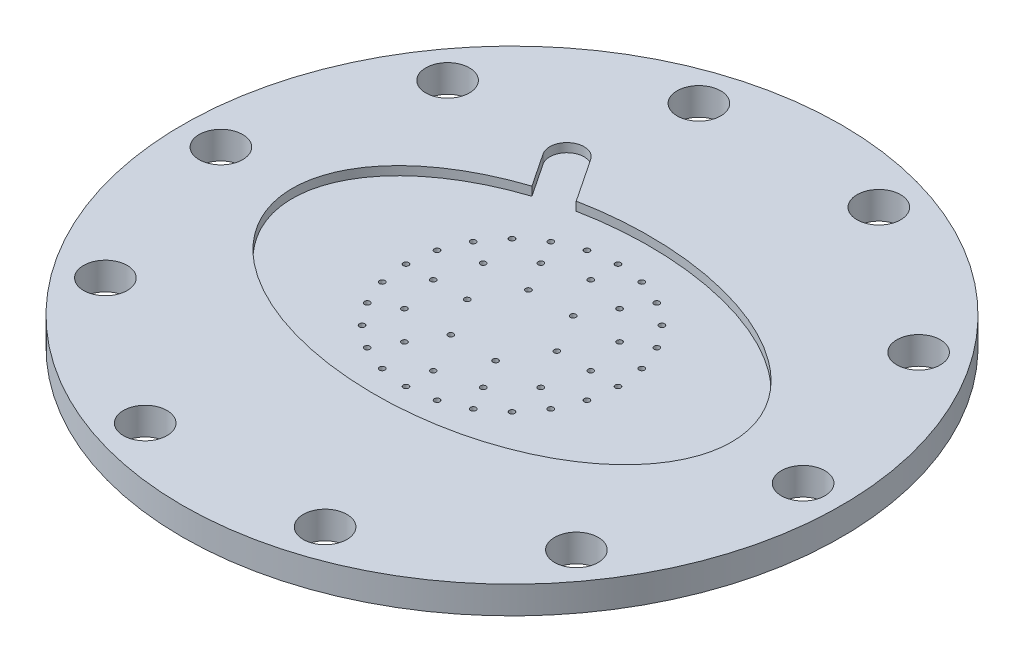
SolidWorks part; units mm, degrees
ref_plane "Front Plane" through (0, 0, 0) normal (0, 0, 1) x (1, 0, 0)
ref_plane "Top Plane" through (0, 0, 0) normal (0, 1, 0) x (1, 0, 0)
ref_plane "Right Plane" through (0, 0, 0) normal (1, 0, 0) x (0, 0, -1)
sketch "Sketch1" plane through (0, 0, 0) normal (0, 0, 1) x (1, 0, 0)
  line L0 (0, -6.35) -> (54.8259, -6.35)
  line L1 (0, 0) -> (76.2, 0)
  line L2 (0, 0) -> (0, -6.35)
  line L4 (76.2, 0) -> (76.2, -6.35)
  line L5 (54.8259, -6.35) -> (54.8259, -3.6576)
  line L6 (54.8259, -3.6576) -> (58.8899, -3.6576)
  line L7 (58.8899, -3.6576) -> (58.8899, -6.35)
  line L8 (58.8899, -6.35) -> (76.2, -6.35)
  dimension "D1" = 6.35
  dimension "D2" = 76.2
  dimension "D3" = 58.8899
  dimension "D4" = 4.064
  dimension "D5" = 2.6924
revolve "Revolve1" add sketch "Sketch1" angle 360 about L2
sketch "Sketch2" plane through (0, 0, 0) normal (0, 1, 0) x (1, 0, 0)
  line L0 (0, 0) -> (67.31, 0) construction
  dimension "D1" = 67.31
ref_axis "Axis1" through (0, 0.3175, 0) along (0, -1, 0)
hole_wizard "3/8 Clearance Hole1" positions "3DSketch2" profile "Sketch4" hole size "3/8" standard "ANSI Inch" end condition through all
sketch3d "3DSketch2"
  point P0 (67.31, 0, 0)
sketch "Sketch4" plane through (67.31, 0, 0) normal (1, 0, 0) x (0, 0, 1)
  line L0 (0, 0) -> (0, 6.35)
  line L1 (0, 6.35) -> (5.0419, 6.35)
  line L2 (5.0419, 6.35) -> (5.0419, 0)
  line L5 (5.0419, 0) -> (0, 0)
  line L11 (0, -6.35) -> (0, 107.95) construction
  dimension "Thru Hole Dia." = 10.0838
  dimension "Thru Hole Depth" = 6.35
pattern_circular "CirPattern1" count 10 over 360 about axis through (0, 0.3175, 0) along (0, -1, 0) of "3/8 Clearance Hole1"
sketch "Sketch5" plane through (0, 0, 0) normal (0, 1, 0) x (1, 0, 0)
  line L0 (-50.8, 0) -> (50.8, 0) construction
  line L1 (0, 0) -> (-25.4, 38.1) construction
  line L2 (-3.3022, -2.2015) -> (-28.7022, 35.8985)
  line L3 (3.3022, 2.2015) -> (-22.0978, 40.3015)
  arc A0 (-3.3022, -2.2015) -> (3.3022, 2.2015) centre (0, 0) ccw
  arc A1 (-22.0978, 40.3015) -> (-28.7022, 35.8985) centre (-25.4, 38.1) ccw
  ellipse E0 centre (0, 0) end of major axis (50.8, 0) minor radius 31.75
  point P10 (-12.7, 19.05)
  dimension "D5" = 3.9688
  dimension "D1" = 31.75
  dimension "D2" = 50.8
  dimension "D3" = 25.4
  dimension "D4" = 38.1
extrude "Cut-Extrude1" cut sketch "Sketch5" against normal blind 2.032 contours E0 | L3 A1 L2 A0
sketch "Sketch6" plane through (0, -2.032, 0) normal (0, 1, 0) x (1, 0, 0)
  circle A1 centre (-5.1816, -8.9748) radius 0.635
  circle A2 centre (-5.1816, -8.9748) radius 0.635
  circle A3 centre (5.1816, -8.9748) radius 0.635
  circle A4 centre (5.1816, -8.9748) radius 0.635
  circle A5 centre (24.511, 0) radius 0.635
  circle A6 centre (24.511, 0) radius 0.635
  circle A7 centre (18.2118, 0) radius 0.635
  circle A8 centre (18.2118, 0) radius 0.635
  circle A9 centre (10.3632, 0) radius 0.635
  circle A10 centre (10.3632, 0) radius 0.635
  circle A11 centre (0, -18.2118) radius 0.635
  circle A12 centre (0, -18.2118) radius 0.635
  circle A13 centre (9.1059, -15.7719) radius 0.635
  circle A14 centre (9.1059, -15.7719) radius 0.635
  circle A15 centre (15.7719, -9.1059) radius 0.635
  circle A16 centre (15.7719, -9.1059) radius 0.635
  circle A17 centre (5.1816, 8.9748) radius 0.635
  circle A18 centre (5.1816, 8.9748) radius 0.635
  circle A19 centre (-5.1816, 8.9748) radius 0.635
  circle A20 centre (-5.1816, 8.9748) radius 0.635
  circle A21 centre (-10.3632, 0) radius 0.635
  circle A22 centre (-10.3632, 0) radius 0.635
  circle A23 centre (15.7719, 9.1059) radius 0.635
  circle A24 centre (15.7719, 9.1059) radius 0.635
  circle A25 centre (9.1059, 15.7719) radius 0.635
  circle A26 centre (9.1059, 15.7719) radius 0.635
  circle A27 centre (0, 18.2118) radius 0.635
  circle A28 centre (0, 18.2118) radius 0.635
  circle A29 centre (-9.1059, 15.7719) radius 0.635
  circle A30 centre (-9.1059, 15.7719) radius 0.635
  circle A31 centre (-15.7719, 9.1059) radius 0.635
  circle A32 centre (-15.7719, 9.1059) radius 0.635
  circle A33 centre (-18.2118, 0) radius 0.635
  circle A34 centre (-18.2118, 0) radius 0.635
  circle A35 centre (-15.7719, -9.1059) radius 0.635
  circle A36 centre (-15.7719, -9.1059) radius 0.635
  circle A37 centre (-9.1059, -15.7719) radius 0.635
  circle A38 centre (-9.1059, -15.7719) radius 0.635
  circle A39 centre (-6.3439, -23.6758) radius 0.635
  circle A40 centre (-6.3439, -23.6758) radius 0.635
  circle A41 centre (0, -24.511) radius 0.635
  circle A42 centre (0, -24.511) radius 0.635
  circle A43 centre (6.3439, -23.6758) radius 0.635
  circle A44 centre (6.3439, -23.6758) radius 0.635
  circle A45 centre (12.2555, -21.2271) radius 0.635
  circle A46 centre (12.2555, -21.2271) radius 0.635
  circle A47 centre (17.3319, -17.3319) radius 0.635
  circle A48 centre (17.3319, -17.3319) radius 0.635
  circle A49 centre (21.2271, -12.2555) radius 0.635
  circle A50 centre (21.2271, -12.2555) radius 0.635
  circle A51 centre (23.6758, -6.3439) radius 0.635
  circle A52 centre (23.6758, -6.3439) radius 0.635
  circle A53 centre (-17.3319, 17.3319) radius 0.635
  circle A54 centre (-17.3319, 17.3319) radius 0.635
  circle A55 centre (-21.2271, 12.2555) radius 0.635
  circle A56 centre (-21.2271, 12.2555) radius 0.635
  circle A57 centre (-23.6758, 6.3439) radius 0.635
  circle A58 centre (-23.6758, 6.3439) radius 0.635
  circle A59 centre (-24.511, 0) radius 0.635
  circle A60 centre (-24.511, 0) radius 0.635
  circle A61 centre (-23.6758, -6.3439) radius 0.635
  circle A62 centre (-23.6758, -6.3439) radius 0.635
  circle A63 centre (-21.2271, -12.2555) radius 0.635
  circle A64 centre (-21.2271, -12.2555) radius 0.635
  circle A65 centre (-17.3319, -17.3319) radius 0.635
  circle A66 centre (-17.3319, -17.3319) radius 0.635
  circle A67 centre (-12.2555, -21.2271) radius 0.635
  circle A68 centre (-12.2555, -21.2271) radius 0.635
  circle A69 centre (23.6758, 6.3439) radius 0.635
  circle A70 centre (23.6758, 6.3439) radius 0.635
  circle A71 centre (21.2271, 12.2555) radius 0.635
  circle A72 centre (21.2271, 12.2555) radius 0.635
  circle A73 centre (17.3319, 17.3319) radius 0.635
  circle A74 centre (17.3319, 17.3319) radius 0.635
  circle A75 centre (12.2555, 21.2271) radius 0.635
  circle A76 centre (12.2555, 21.2271) radius 0.635
  circle A77 centre (6.3439, 23.6758) radius 0.635
  circle A78 centre (6.3439, 23.6758) radius 0.635
  circle A79 centre (0, 24.511) radius 0.635
  circle A80 centre (0, 24.511) radius 0.635
  circle A81 centre (-6.3439, 23.6758) radius 0.635
  circle A82 centre (-6.3439, 23.6758) radius 0.635
  circle A83 centre (-12.2555, 21.2271) radius 0.635
  circle A84 centre (-12.2555, 21.2271) radius 0.635
  dimension "D1" = 0
  dimension "D2" = 0
  dimension "D3" = 0
  dimension "D4" = 0
  dimension "D5" = 0
  dimension "D6" = 0
  dimension "D7" = 0
  dimension "D8" = 0
  dimension "D9" = 0
  dimension "D10" = 0
  dimension "D11" = 0
  dimension "D12" = 0
  dimension "D13" = 0
  dimension "D14" = 0
  dimension "D15" = 0
  dimension "D16" = 0
  dimension "D17" = 0
  dimension "D18" = 0
  dimension "D19" = 0
  dimension "D20" = 0
  dimension "D21" = 0
  dimension "D22" = 0
  dimension "D23" = 0
  dimension "D24" = 0
  dimension "D25" = 0
  dimension "D26" = 0
  dimension "D27" = 0
  dimension "D28" = 0
  dimension "D29" = 0
  dimension "D30" = 0
  dimension "D31" = 0
  dimension "D32" = 0
  dimension "D33" = 0
  dimension "D34" = 0
  dimension "D35" = 0
  dimension "D36" = 0
  dimension "D37" = 0
  dimension "D38" = 0
  dimension "D39" = 0
  dimension "D40" = 0
  dimension "D41" = 0
  dimension "D42" = 0
extrude "Cut-Extrude2" cut sketch "Sketch6" against normal through all
